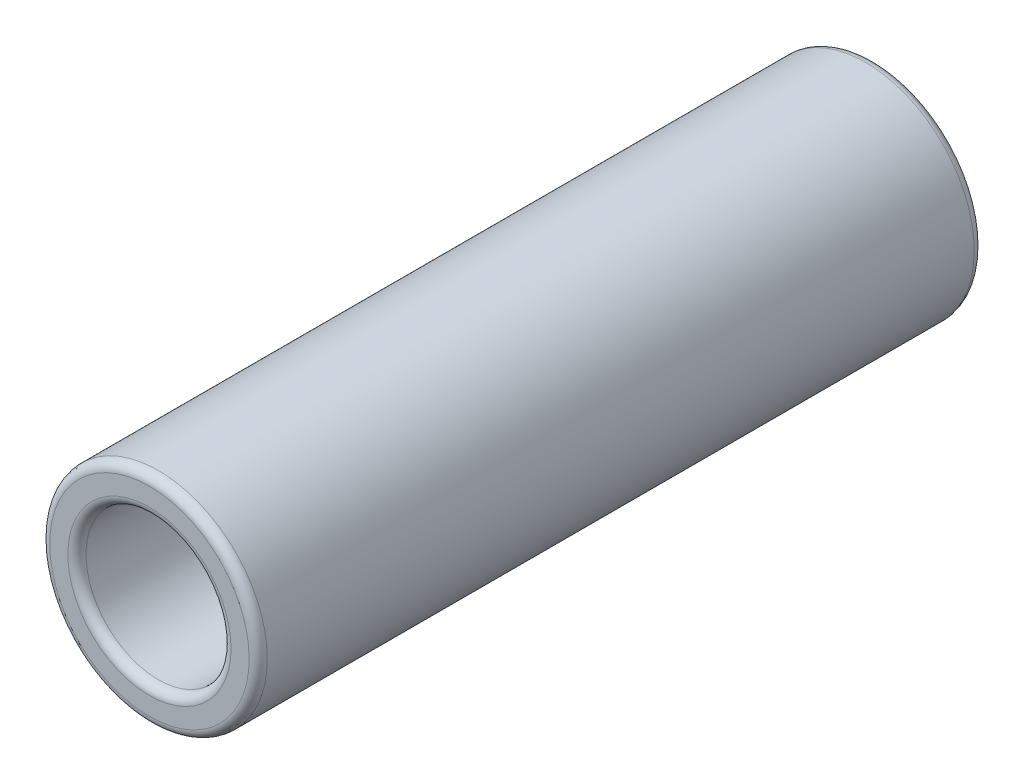
SolidWorks part; units mm, degrees
ref_plane "Front Plane" through (0, 0, 0) normal (0, 0, 1) x (1, 0, 0)
ref_plane "Top Plane" through (0, 0, 0) normal (0, 1, 0) x (1, 0, 0)
ref_plane "Right Plane" through (0, 0, 0) normal (1, 0, 0) x (0, 0, -1)
sketch "Sketch1" plane through (0, 0, 0) normal (0, 0, 1) x (1, 0, 0)
  circle A0 centre (0, 0) radius 4
  circle A1 centre (0, 0) radius 6
  dimension "D1" = 8
  dimension "D2" = 12
extrude "Boss-Extrude1" add sketch "Sketch1" along normal mid plane 40
fillet "Fillet1" radius 0.5 4 edges at (4, 0, -20) (4, 0, 20) (6, 0, -20) (6, 0, 20)
